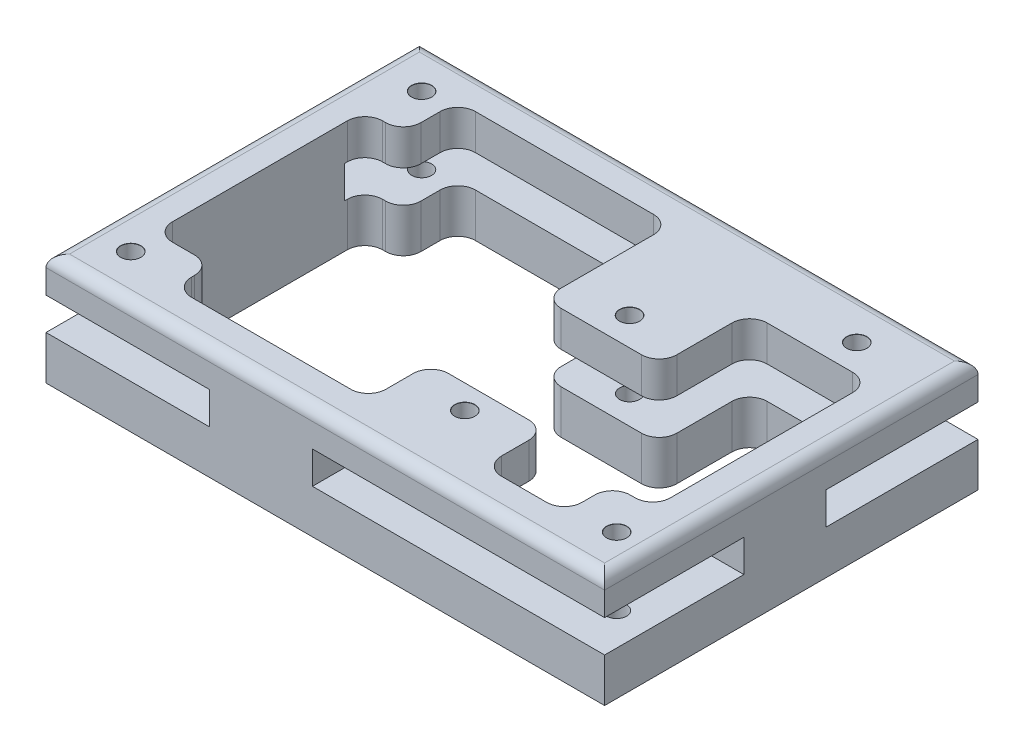
SolidWorks part; units mm, degrees
ref_plane "Front Plane" through (0, 0, 0) normal (0, 0, 1) x (1, 0, 0)
ref_plane "Top Plane" through (0, 0, 0) normal (0, 1, 0) x (1, 0, 0)
ref_plane "Right Plane" through (0, 0, 0) normal (1, 0, 0) x (0, 0, -1)
sketch "Sketch2" plane through (0, 0, 0) normal (0, 1, 0) x (1, 0, 0)
  line L1 (47.5, 31.75) -> (-47.5, 31.75)
  line L2 (47.5, 31.75) -> (47.5, -31.75)
  line L3 (47.5, -31.75) -> (-47.5, -31.75)
  line L4 (-47.5, 31.75) -> (-47.5, -31.75)
  line L5 (47.5, 31.75) -> (-47.5, -31.75) construction
  line L6 (47.5, -31.75) -> (-47.5, 31.75) construction
  point P0 (0, 0)
  dimension "D1" = 95
  dimension "D2" = 63.5
extrude "Boss-Extrude1" add sketch "Sketch2" along normal blind 19
hole_wizard "M3 Clearance Hole1" positions "Sketch7" profile "Sketch8" hole size "M3" standard "ANSI Metric" end condition through all
sketch "Sketch7" plane through (0, 19, 0) normal (0, 1, 0) x (1, 0, 0)
  line L1 (-40.6667, 24.17) -> (34.4633, 24.17)
  line L2 (-40.6667, 24.17) -> (-40.6667, -24.17)
  line L3 (-40.6667, -24.17) -> (34.4633, -24.17)
  line L4 (34.4633, 24.17) -> (34.4633, -24.17)
  line L5 (34.4633, -24.17) -> (41.9633, -24.17) construction
  line L12 (41.9633, -24.17) -> (47.5, -24.17) construction
  line L13 (47.5, -31.75) -> (47.5, 31.75) construction
  line L15 (0, 31.75) -> (0, 24.17) construction
  line L16 (47.5, 31.75) -> (-47.5, 31.75) construction
  line L17 (-3.1017, -24.17) -> (-3.1017, -31.75) construction
  line L18 (-47.5, -31.75) -> (47.5, -31.75) construction
  line L19 (11.1433, -19.17) -> (11.1433, -24.17) construction
  point P33 (-40.6667, -24.17)
  point P34 (34.4633, 24.17)
  point P43 (41.9633, -24.17)
  point P74 (11.1433, -19.17)
  point P80 (11.1433, 8.85)
  point P85 (-3.1017, -24.17)
  point P88 (-39.5367, 24.17)
  dimension "D1" = 48.34
  dimension "D2" = 75.13
  dimension "D3" = 7.5
  dimension "D4" = 51.81
  dimension "D5" = 5
  dimension "D6" = 28.02
  dimension "D7" = 1.13
sketch "Sketch8" plane through (-39.5367, 19, -24.17) normal (1, 0, 0) x (0, 0, 1)
  line L0 (0, 0) -> (0, 19)
  line L1 (0, 19) -> (1.7, 19)
  line L2 (1.7, 19) -> (1.7, 0.025)
  line L3 (1.7, 0.025) -> (1.725, 0)
  line L5 (1.725, 0) -> (0, 0)
  line L6 (-1.7, 0.025) -> (-1.725, 0) construction
  line L11 (0, -6.35) -> (0, 107.95) construction
  dimension "Thru Hole Dia." = 3.4
  dimension "Thru Hole Depth" = 19
  dimension "Near C'Sink Dia." = 3.45
  dimension "Near C'Sink Angle" = 90
sketch "Sketch9" plane through (0, 19, 0) normal (0, 1, 0) x (1, 0, 0)
  line L0 (-34.9742, 19.4874) -> (-34.9742, 22.75)
  line L2 (-37.9742, 16.4874) -> (-38.5, 16.4874)
  line L3 (-41.5, 13.4874) -> (-41.5, -16.2525)
  line L4 (-38.5, -19.2525) -> (-34.7301, -19.2525)
  line L5 (-31.7301, -22.2525) -> (-31.7301, -22.75)
  line L6 (-31.9742, 25.75) -> (-1.6848, 25.75)
  line L7 (-28.7301, -25.75) -> (-1.6848, -25.75)
  line L8 (1.3152, -22.75) -> (1.3152, -18.118)
  line L9 (4.3152, -15.118) -> (17.9713, -15.118)
  line L10 (20.9713, -18.118) -> (20.9713, -22.75)
  line L11 (23.9713, -25.75) -> (31.6479, -25.75)
  line L12 (34.6479, -22.75) -> (34.6479, -20.5605)
  line L13 (37.6479, -17.5605) -> (38.5, -17.5605)
  line L14 (41.5, -14.5605) -> (41.5, 16.4283)
  line L15 (38.5, 19.4283) -> (23.9713, 19.4283)
  line L16 (20.9713, 16.4283) -> (20.9713, 7.055)
  line L17 (17.9713, 4.055) -> (4.3152, 4.055)
  line L18 (1.3152, 7.055) -> (1.3152, 22.75)
  line L19 (-47.5, 31.75) -> (-47.5, -31.75) construction
  line L20 (47.5, 31.75) -> (-47.5, 31.75) construction
  line L21 (47.5, -31.75) -> (47.5, 31.75) construction
  line L22 (-47.5, -31.75) -> (47.5, -31.75) construction
  circle A0 centre (41.9633, -24.17) radius 1.725 construction
  circle A1 centre (34.4633, 24.17) radius 1.725 construction
  circle A2 centre (11.1433, 8.85) radius 1.725 construction
  circle A3 centre (11.1433, -19.17) radius 1.725 construction
  circle A4 centre (-40.6667, -24.17) radius 1.725 construction
  circle A6 centre (41.9633, -24.17) radius 1.725 construction
  circle A7 centre (34.4633, 24.17) radius 1.725 construction
  circle A8 centre (11.1433, 8.85) radius 1.725 construction
  circle A9 centre (11.1433, -19.17) radius 1.725 construction
  circle A10 centre (-40.6667, -24.17) radius 1.725 construction
  arc A12 (-34.9742, 22.75) -> (-31.9742, 25.75) centre (-31.9742, 22.75) cw
  arc A13 (-1.6848, 25.75) -> (1.3152, 22.75) centre (-1.6848, 22.75) cw
  arc A14 (4.3152, 4.055) -> (1.3152, 7.055) centre (4.3152, 7.055) cw
  arc A15 (20.9713, 7.055) -> (17.9713, 4.055) centre (17.9713, 7.055) cw
  arc A16 (23.9713, 19.4283) -> (20.9713, 16.4283) centre (23.9713, 16.4283) ccw
  arc A17 (41.5, 16.4283) -> (38.5, 19.4283) centre (38.5, 16.4283) ccw
  arc A18 (38.5, -17.5605) -> (41.5, -14.5605) centre (38.5, -14.5605) ccw
  arc A19 (34.6479, -20.5605) -> (37.6479, -17.5605) centre (37.6479, -20.5605) cw
  arc A20 (31.6479, -25.75) -> (34.6479, -22.75) centre (31.6479, -22.75) ccw
  arc A21 (20.9713, -22.75) -> (23.9713, -25.75) centre (23.9713, -22.75) ccw
  arc A22 (17.9713, -15.118) -> (20.9713, -18.118) centre (17.9713, -18.118) cw
  arc A23 (1.3152, -18.118) -> (4.3152, -15.118) centre (4.3152, -18.118) cw
  arc A24 (-1.6848, -25.75) -> (1.3152, -22.75) centre (-1.6848, -22.75) ccw
  arc A25 (-31.7301, -22.75) -> (-28.7301, -25.75) centre (-28.7301, -22.75) ccw
  arc A26 (-34.7301, -19.2525) -> (-31.7301, -22.2525) centre (-34.7301, -22.2525) cw
  arc A27 (-41.5, -16.2525) -> (-38.5, -19.2525) centre (-38.5, -16.2525) ccw
  arc A28 (-38.5, 16.4874) -> (-41.5, 13.4874) centre (-38.5, 13.4874) ccw
  arc A29 (-34.9742, 19.4874) -> (-37.9742, 16.4874) centre (-37.9742, 19.4874) cw
  point P37 (11.1433, -15.118)
  point P39 (11.1433, 4.055)
  dimension "D5" = 3
  dimension "D1" = 6
  dimension "D2" = 6
  dimension "D3" = 6
  dimension "D4" = 6
extrude "Cut-Extrude1" cut sketch "Sketch9" against normal up to surface (19 mm away) up to face at (-40.6667, 0, 25.87)
sketch "Sketch10" plane through (0, 0, 0) normal (0, -1, 0) x (1, 0, 0)
  line L1 (-41.4017, 20.903) -> (-38.2049, 21.9)
  line L2 (-38.2049, 21.9) -> (-37.47, 25.167)
  line L3 (-37.47, 25.167) -> (-39.9318, 27.437)
  line L4 (-39.9318, 27.437) -> (-43.1285, 26.44)
  line L5 (-43.1285, 26.44) -> (-43.8635, 23.173)
  line L6 (-43.8635, 23.173) -> (-41.4017, 20.903)
  line L7 (-40.8434, -27.2532) -> (-37.52, -26.8432)
  line L8 (-37.52, -26.8432) -> (-36.2133, -23.76)
  line L9 (-36.2133, -23.76) -> (-38.2301, -21.0868)
  line L10 (-38.2301, -21.0868) -> (-41.5535, -21.4968)
  line L11 (-41.5535, -21.4968) -> (-42.8602, -24.58)
  line L12 (-42.8602, -24.58) -> (-40.8434, -27.2532)
  line L13 (8.0727, -10.1861) -> (10.7651, -12.1772)
  line L14 (10.7651, -12.1772) -> (13.8356, -10.8411)
  line L15 (13.8356, -10.8411) -> (14.2138, -7.5139)
  line L16 (14.2138, -7.5139) -> (11.5215, -5.5228)
  line L17 (11.5215, -5.5228) -> (8.4509, -6.8589)
  line L18 (8.4509, -6.8589) -> (8.0727, -10.1861)
  line L19 (8.0802, 17.8169) -> (10.7835, 15.8407)
  line L20 (10.7835, 15.8407) -> (13.8466, 17.1938)
  line L21 (13.8466, 17.1938) -> (14.2064, 20.5231)
  line L22 (14.2064, 20.5231) -> (11.503, 22.4993)
  line L23 (11.503, 22.4993) -> (8.4399, 21.1462)
  line L24 (8.4399, 21.1462) -> (8.0802, 17.8169)
  line L25 (32.6053, -26.9559) -> (35.9469, -27.172)
  line L26 (35.9469, -27.172) -> (37.8049, -24.3861)
  line L27 (37.8049, -24.3861) -> (36.3212, -21.3841)
  line L28 (36.3212, -21.3841) -> (32.9796, -21.168)
  line L29 (32.9796, -21.168) -> (31.1216, -23.9539)
  line L30 (31.1216, -23.9539) -> (32.6053, -26.9559)
  line L31 (40.0405, 21.4284) -> (43.3761, 21.134)
  line L32 (43.3761, 21.134) -> (45.2989, 23.8756)
  line L33 (45.2989, 23.8756) -> (43.8861, 26.9116)
  line L34 (43.8861, 26.9116) -> (40.5504, 27.206)
  line L35 (40.5504, 27.206) -> (38.6276, 24.4644)
  line L36 (38.6276, 24.4644) -> (40.0405, 21.4284)
  circle A0 centre (34.4633, -24.17) radius 1.7 construction
  circle A1 centre (41.9633, 24.17) radius 1.7 construction
  circle A2 centre (11.1433, 19.17) radius 1.7 construction
  circle A3 centre (11.1433, -8.85) radius 1.7 construction
  circle A5 centre (-40.6667, 24.17) radius 1.7 construction
  circle A6 centre (34.4633, -24.17) radius 1.7 construction
  circle A7 centre (41.9633, 24.17) radius 1.7 construction
  circle A8 centre (11.1433, 19.17) radius 1.7 construction
  circle A9 centre (11.1433, -8.85) radius 1.7 construction
  circle A11 centre (-40.6667, 24.17) radius 1.7 construction
  circle A12 centre (-40.6667, 24.17) radius 2.9 construction
  circle A13 centre (-39.5367, -24.17) radius 2.9 construction
  circle A14 centre (11.1433, -8.85) radius 2.9 construction
  circle A15 centre (11.1433, 19.17) radius 2.9 construction
  circle A16 centre (34.4633, -24.17) radius 2.9 construction
  circle A17 centre (41.9633, 24.17) radius 2.9 construction
  circle A18 centre (-39.5367, -24.17) radius 1.7 construction
  circle A19 centre (-39.5367, -24.17) radius 1.7 construction
  point P61 (0, 0)
  dimension "D1" = 5.8
extrude "Cut-Extrude2" cut sketch "Sketch10" against normal blind 2.4
fillet "Fillet2" radius 2 4 edges at (0, 19, -31.75) (47.5, 19, 0) (0, 19, 31.75) (-47.5, 19, 0)
ref_plane "Plane1" through (0, 10.2, 0) normal (0, 1, 0) x (1, 0, 0)
sketch "Sketch12" plane through (0, 10.2, 0) normal (0, 1, 0) x (1, 0, 0)
  line L0 (-31.7301, -22.2525) -> (-31.7301, -22.75) construction
  line L1 (-38.5, -19.2525) -> (-34.7301, -19.2525) construction
  line L2 (-31.7301, -22.2525) -> (-31.7301, -22.75)
  line L3 (-38.5, -19.2525) -> (-34.7301, -19.2525)
  line L14 (-40.6667, -24.17) -> (-40.6213, -18.3738) construction
  line L15 (47.5, -31.75) -> (-47.5, -31.75) construction
  line L16 (-47.5, -31.75) -> (-47.5, 31.75) construction
  line L17 (-19.7301, -31.75) -> (-47.5, -31.75)
  line L18 (-47.5, -31.75) -> (-47.5, -15.7525)
  line L23 (-19.7301, -31.75) -> (-19.7301, -25.75)
  line L24 (-28.7301, -25.75) -> (-1.6848, -25.75) construction
  line L25 (-19.7301, -25.75) -> (-28.7301, -25.75)
  line L26 (-47.5, -15.7525) -> (-41.5, -15.7525)
  line L27 (-41.5, 13.4874) -> (-41.5, -16.2525) construction
  line L28 (-41.5, -15.7525) -> (-41.5, -16.2525)
  arc A0 (-31.7301, -22.75) -> (-28.7301, -25.75) centre (-28.7301, -22.75) ccw construction
  arc A1 (-31.7301, -22.2525) -> (-34.7301, -19.2525) centre (-34.7301, -22.2525) ccw construction
  arc A2 (-41.5, -16.2525) -> (-38.5, -19.2525) centre (-38.5, -16.2525) ccw construction
  arc A3 (-31.7301, -22.75) -> (-28.7301, -25.75) centre (-28.7301, -22.75) ccw
  arc A4 (-31.7301, -22.2525) -> (-34.7301, -19.2525) centre (-34.7301, -22.2525) ccw
  arc A5 (-41.5, -16.2525) -> (-38.5, -19.2525) centre (-38.5, -16.2525) ccw
  circle A6 centre (-40.6667, -24.17) radius 1.7 construction
  circle A7 centre (-40.6667, -24.17) radius 1.7
  dimension "D1" = 9
  dimension "D2" = 0.5
extrude "Cut-Extrude3" cut sketch "Sketch12" along normal blind 2.75 and the other way blind 2.75
sketch "Sketch14" plane through (0, 10.2, 0) normal (0, 1, 0) x (1, 0, 0)
  line L0 (-34.9742, 22.75) -> (-34.9742, 19.4874) construction
  line L1 (-34.9742, 22.75) -> (-34.9742, 19.4874)
  line L3 (-47.5, -31.75) -> (-47.5, 31.75) construction
  line L4 (-47.5, 12.9874) -> (-47.5, 31.75)
  line L5 (-31.9742, 25.75) -> (-31.9742, 31.75) construction
  line L6 (-47.5, 31.75) -> (47.5, 31.75) construction
  line L8 (-47.5, 31.75) -> (-11.9742, 31.75)
  line L9 (-37.9742, 16.4874) -> (-38.5, 16.4874) construction
  line L10 (-37.9742, 16.4874) -> (-38.5, 16.4874)
  line L11 (-31.9742, 25.75) -> (-11.9742, 25.75)
  line L12 (-1.6848, 25.75) -> (-31.9742, 25.75) construction
  line L13 (-11.9742, 25.75) -> (-11.9742, 31.75)
  line L16 (-47.5, 12.9874) -> (-41.5, 12.9874)
  line L17 (-41.5, 13.4874) -> (-41.5, -16.2525) construction
  line L18 (-41.5, 12.9874) -> (-41.5, 13.4874)
  arc A1 (-38.5, 16.4874) -> (-41.5, 13.4874) centre (-38.5, 13.4874) ccw construction
  arc A2 (-37.9742, 16.4874) -> (-34.9742, 19.4874) centre (-37.9742, 19.4874) ccw construction
  arc A3 (-31.9742, 25.75) -> (-34.9742, 22.75) centre (-31.9742, 22.75) ccw construction
  arc A5 (-38.5, 16.4874) -> (-41.5, 13.4874) centre (-38.5, 13.4874) ccw
  arc A6 (-37.9742, 16.4874) -> (-34.9742, 19.4874) centre (-37.9742, 19.4874) ccw
  arc A7 (-31.9742, 25.75) -> (-34.9742, 22.75) centre (-31.9742, 22.75) ccw
  dimension "D1" = 20
  dimension "D2" = 0.5
extrude "Cut-Extrude10" cut sketch "Sketch14" against normal blind 2.75 and the other way blind 2.75
sketch "Sketch13" plane through (0, 10.2, 0) normal (0, 1, 0) x (1, 0, 0)
  line L1 (20.9713, -18.118) -> (20.9713, -22.75) construction
  line L2 (4.3152, -15.118) -> (17.9713, -15.118) construction
  line L3 (1.3152, -22.75) -> (1.3152, -18.118) construction
  line L4 (47.5, 31.75) -> (47.5, -31.75) construction
  line L5 (20.9713, -18.118) -> (20.9713, -22.75)
  line L6 (4.3152, -15.118) -> (17.9713, -15.118)
  line L7 (1.3152, -22.75) -> (1.3152, -18.118)
  line L9 (37.6479, -17.5605) -> (38.5, -17.5605) construction
  line L10 (34.6479, -22.75) -> (34.6479, -20.5605) construction
  line L12 (23.9713, -25.75) -> (31.6479, -25.75) construction
  line L13 (-2.1848, -31.75) -> (47.5, -31.75)
  line L14 (47.5, -31.75) -> (-47.5, -31.75) construction
  line L15 (47.5, -8.0605) -> (47.5, -31.75)
  line L16 (37.6479, -17.5605) -> (38.5, -17.5605)
  line L18 (34.6479, -22.75) -> (34.6479, -20.5605)
  line L20 (23.9713, -25.75) -> (31.6479, -25.75)
  line L22 (41.5, -14.5605) -> (41.5, -8.0605)
  line L23 (41.5, -14.5605) -> (41.5, 16.4283) construction
  line L24 (41.5, -8.0605) -> (47.5, -8.0605)
  line L25 (-2.1848, -31.75) -> (-2.1848, -25.75)
  line L26 (-28.7301, -25.75) -> (-1.6848, -25.75) construction
  line L27 (-2.1848, -25.75) -> (-1.6848, -25.75)
  arc A0 (-1.6848, -25.75) -> (1.3152, -22.75) centre (-1.6848, -22.75) ccw construction
  arc A1 (20.9713, -22.75) -> (23.9713, -25.75) centre (23.9713, -22.75) ccw construction
  arc A2 (20.9713, -18.118) -> (17.9713, -15.118) centre (17.9713, -18.118) ccw construction
  arc A3 (4.3152, -15.118) -> (1.3152, -18.118) centre (4.3152, -18.118) ccw construction
  arc A4 (-1.6848, -25.75) -> (1.3152, -22.75) centre (-1.6848, -22.75) ccw
  arc A5 (20.9713, -22.75) -> (23.9713, -25.75) centre (23.9713, -22.75) ccw
  arc A6 (20.9713, -18.118) -> (17.9713, -15.118) centre (17.9713, -18.118) ccw
  arc A7 (4.3152, -15.118) -> (1.3152, -18.118) centre (4.3152, -18.118) ccw
  arc A15 (38.5, -17.5605) -> (41.5, -14.5605) centre (38.5, -14.5605) ccw construction
  arc A16 (37.6479, -17.5605) -> (34.6479, -20.5605) centre (37.6479, -20.5605) ccw construction
  arc A17 (31.6479, -25.75) -> (34.6479, -22.75) centre (31.6479, -22.75) ccw construction
  arc A18 (38.5, -17.5605) -> (41.5, -14.5605) centre (38.5, -14.5605) ccw
  arc A19 (37.6479, -17.5605) -> (34.6479, -20.5605) centre (37.6479, -20.5605) ccw
  arc A20 (31.6479, -25.75) -> (34.6479, -22.75) centre (31.6479, -22.75) ccw
  dimension "D1" = 6.5
  dimension "D2" = 0.5
extrude "Cut-Extrude11" cut sketch "Sketch13" against normal blind 2.75 and the other way blind 2.75
sketch "Sketch15" plane through (0, 10.2, 0) normal (0, 1, 0) x (1, 0, 0)
  line L0 (38.5, 19.4283) -> (23.9713, 19.4283) construction
  line L1 (20.9713, 16.4283) -> (20.9713, 7.055) construction
  line L2 (17.9713, 4.055) -> (4.3152, 4.055) construction
  line L3 (1.3152, 7.055) -> (1.3152, 22.75) construction
  line L4 (38.5, 19.4283) -> (23.9713, 19.4283)
  line L5 (20.9713, 16.4283) -> (20.9713, 7.055)
  line L6 (17.9713, 4.055) -> (4.3152, 4.055)
  line L7 (1.3152, 7.055) -> (1.3152, 22.75)
  line L8 (-1.6848, 25.75) -> (-12.6848, 25.75)
  line L10 (-1.6848, 25.75) -> (-31.9742, 25.75) construction
  line L11 (-12.6848, 25.75) -> (-12.6848, 31.75)
  line L12 (-47.5, 31.75) -> (47.5, 31.75) construction
  line L13 (-12.6848, 31.75) -> (47.5, 31.75)
  line L14 (47.5, 31.75) -> (47.5, 5.9283)
  line L15 (47.5, 31.75) -> (47.5, -31.75) construction
  line L16 (47.5, 5.9283) -> (41.5, 5.9283)
  line L17 (41.5, -14.5605) -> (41.5, 16.4283) construction
  line L18 (41.5, 5.9283) -> (41.5, 16.4283)
  line L19 (11.1433, 8.85) -> (11.1433, 4.055) construction
  line L20 (31.2357, 19.4283) -> (31.2357, 24.17) construction
  line L21 (31.2357, 24.17) -> (34.4633, 24.17) construction
  line L22 (-39.5367, 24.17) -> (-39.5367, 8.85) construction
  line L23 (-39.5367, 8.85) -> (11.1433, 8.85) construction
  circle A0 centre (34.4633, 24.17) radius 1.725 construction
  circle A1 centre (11.1433, 8.85) radius 1.725 construction
  arc A2 (41.5, 16.4283) -> (38.5, 19.4283) centre (38.5, 16.4283) ccw construction
  arc A3 (23.9713, 19.4283) -> (20.9713, 16.4283) centre (23.9713, 16.4283) ccw construction
  arc A4 (17.9713, 4.055) -> (20.9713, 7.055) centre (17.9713, 7.055) ccw construction
  arc A5 (1.3152, 7.055) -> (4.3152, 4.055) centre (4.3152, 7.055) ccw construction
  arc A6 (1.3152, 22.75) -> (-1.6848, 25.75) centre (-1.6848, 22.75) ccw construction
  circle A7 centre (34.4633, 24.17) radius 1.725 construction
  circle A8 centre (11.1433, 8.85) radius 1.725 construction
  arc A9 (41.5, 16.4283) -> (38.5, 19.4283) centre (38.5, 16.4283) ccw
  arc A10 (23.9713, 19.4283) -> (20.9713, 16.4283) centre (23.9713, 16.4283) ccw
  arc A11 (17.9713, 4.055) -> (20.9713, 7.055) centre (17.9713, 7.055) ccw
  arc A12 (1.3152, 7.055) -> (4.3152, 4.055) centre (4.3152, 7.055) ccw
  arc A13 (1.3152, 22.75) -> (-1.6848, 25.75) centre (-1.6848, 22.75) ccw
  circle A16 centre (-40.6667, -24.17) radius 1.7 construction
  circle A17 centre (-40.6667, -24.17) radius 1.7
  circle A18 centre (-39.5367, 24.17) radius 1.725 construction
  circle A19 centre (-39.5367, 24.17) radius 1.725 construction
  point P45 (0, 0)
  point P47 (0, 0)
  dimension "D1" = 11
  dimension "D2" = 10.5
extrude "Cut-Extrude12" cut sketch "Sketch15" against normal blind 2.75 and the other way blind 2.75
sketch "Sketch16" plane through (0, 19, 0) normal (0, 1, 0) x (1, 0, 0)
  line L1 (23.5, 17.5) -> (-23.5, 17.5)
  line L2 (23.5, 17.5) -> (23.5, -17.5)
  line L3 (23.5, -17.5) -> (-23.5, -17.5)
  line L4 (-23.5, 17.5) -> (-23.5, -17.5)
  line L5 (23.5, 17.5) -> (-23.5, -17.5) construction
  line L6 (23.5, -17.5) -> (-23.5, 17.5) construction
  point P0 (0, 0)
  dimension "D1" = 35
  dimension "D2" = 47
